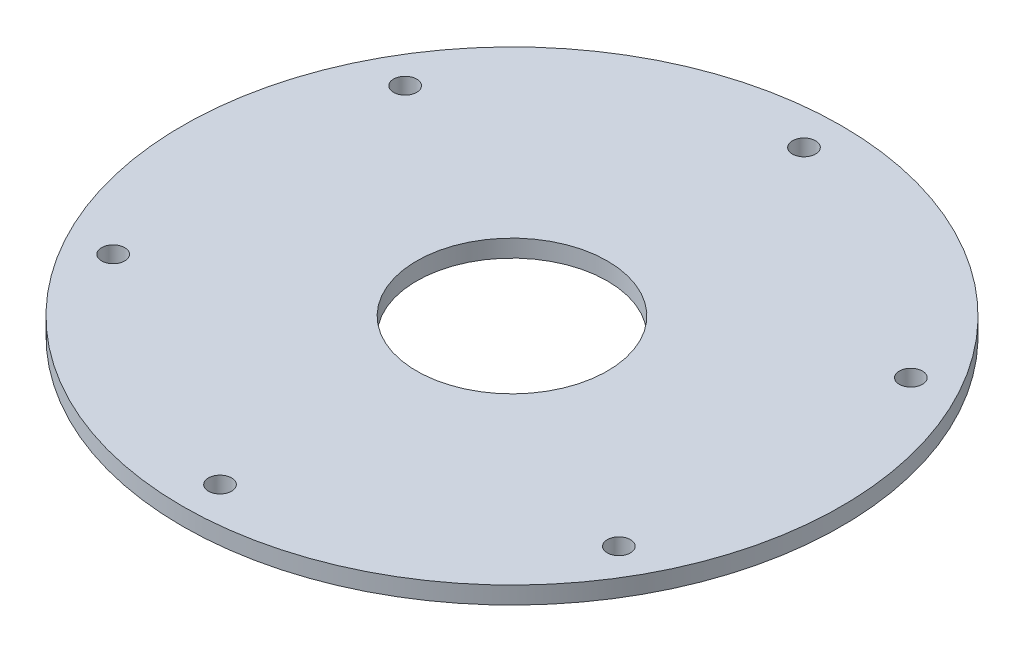
SolidWorks part; units mm, degrees
ref_plane "Front Plane" through (0, 0, 0) normal (0, 0, 1) x (1, 0, 0)
ref_plane "Top Plane" through (0, 0, 0) normal (0, 1, 0) x (1, 0, 0)
ref_plane "Right Plane" through (0, 0, 0) normal (1, 0, 0) x (0, 0, -1)
sketch "Sketch1" plane through (0, 0, 0) normal (0, 1, 0) x (1, 0, 0)
  circle A0 centre (0, 0) radius 57
  dimension "D1" = 114
extrude "Boss-Extrude1" add sketch "Sketch1" along normal blind 3
sketch "Sketch2" plane through (0, 3, 0) normal (0, 1, 0) x (1, 0, 0)
  line L0 (0, 62.5097) -> (0, -64.2706) construction
  circle A0 centre (0, 50.5) radius 2
  dimension "D1" = 4
  dimension "D2" = 50.5
extrude "Cut-Extrude1" cut sketch "Sketch2" against normal through all
pattern_circular "CirPattern1" count 6 over 360 about axis through (0, 3, 0) along (0, 1, 0) of "Cut-Extrude1"
sketch "Sketch4" plane through (0, 0, 0) normal (0, -1, 0) x (1, 0, 0)
  circle A0 centre (0, 0) radius 16.5
  dimension "D1" = 33
extrude "Cut-Extrude3" cut sketch "Sketch4" against normal through all
